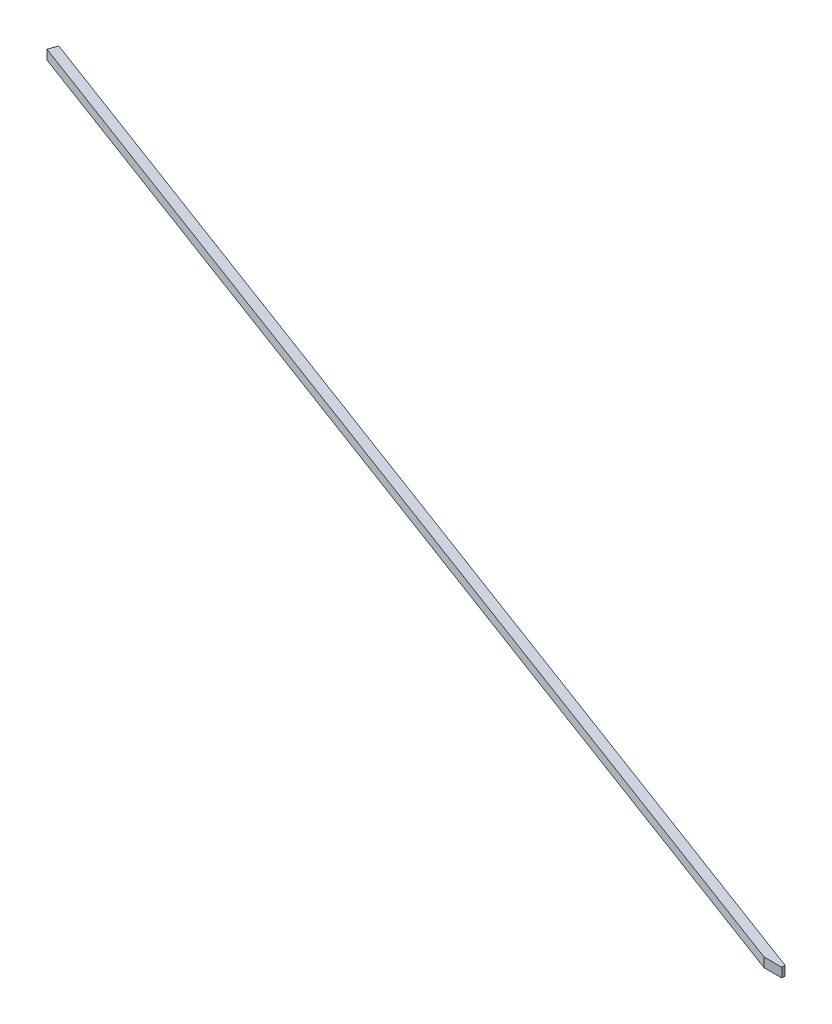
SolidWorks part; units mm, degrees
note: The reader was unsure of these and kept them because the rebuilt part matched: shared geometry of "Sketch5<3>".
material "Balsa"
ref_plane "Front Plane" through (0, 0, 0) normal (0, 0, 1) x (1, 0, 0)
ref_plane "Top Plane" through (0, 0, 0) normal (0, 1, 0) x (1, 0, 0)
ref_plane "Right Plane" through (0, 0, 0) normal (1, 0, 0) x (0, 0, -1)
sketch "Sketch1" plane through (0, 0, 0) normal (0, 0, 1) x (1, 0, 0)
  line L0 (-18.175, 48.175) -> (18.175, 48.175)
  line L4 (405, 11.825) -> (405, 15)
  line L5 (-15, 45) -> (15, 45)
  line L7 (-15, 15) -> (15, 15)
  line L10 (405, 11.825) -> (405, 15)
  line L14 (-18.175, 11.825) -> (18.175, 11.825)
  line L16 (18.175, 48.175) -> (405, 48.175)
  line L17 (18.175, 11.825) -> (405, 11.825)
  line L18 (15, 45) -> (405, 45)
  line L19 (15, 15) -> (405, 15)
  line L20 (-18.175, 48.175) -> (-18.175, 45)
  line L21 (-18.175, 48.175) -> (-18.175, 11.825) construction
  line L22 (-15, 45) -> (-15, 15) construction
  line L23 (15, 45) -> (15, 15) construction
  line L24 (-18.175, 45) -> (-15, 45)
  line L25 (18.175, 48.175) -> (18.175, 11.825) construction
  line L26 (405, 45) -> (405, 48.175)
  line L27 (405, 45) -> (405, 48.175)
  line L28 (-18.175, 11.825) -> (-18.175, 15)
  line L29 (-18.175, 15) -> (-15, 15)
  point P4 (0, 30)
  dimension "D3" = 30
  dimension "D5" = 3.175
extrude "Boss-Extrude1" add sketch "Sketch1" along normal blind 3.175 contours L18 L26 L16 L0 L20 L24 L5 | L29 L28 L14 L17 L4 L19 L7
sketch "Sketch2" plane through (0, 0, 3.175) normal (0, 0, 1) x (1, 0, 0)
  line L0 (-18.175, 48.175) -> (405, 48.175) construction
  line L1 (-18.175, 11.825) -> (-15, 11.825)
  line L2 (-18.175, 11.825) -> (-18.175, 48.175)
  line L3 (-18.175, 48.175) -> (-15, 48.175)
  line L4 (-15, 11.825) -> (-15, 48.175)
  line L5 (-18.175, 11.825) -> (405, 11.825) construction
  line L6 (-15, 48.175) -> (15, 48.175)
  line L7 (-15, 48.175) -> (-15, 11.825)
  line L8 (-15, 11.825) -> (15, 11.825)
  line L9 (15, 48.175) -> (15, 11.825)
  line L10 (18.175, 30) -> (401.825, 30) construction
  line L11 (15, 48.175) -> (18.175, 48.175)
  line L12 (15, 48.175) -> (15, 11.825)
  line L13 (15, 11.825) -> (18.175, 11.825)
  line L14 (18.175, 48.175) -> (18.175, 11.825)
  line L15 (405, 48.175) -> (401.825, 48.175)
  line L16 (405, 48.175) -> (405, 11.825)
  line L17 (405, 11.825) -> (401.825, 11.825)
  line L18 (401.825, 48.175) -> (401.825, 11.825)
  line L19 (210, 30) -> (210, 38.7375) construction
  line L20 (18.175, 38.7375) -> (210, 38.7375) construction
  line L21 (114.0875, 38.7375) -> (114.0875, 45)
  line L22 (-18.175, 45) -> (405, 45) construction
  line L23 (210, 38.7375) -> (401.825, 38.7375) construction
  line L24 (305.9125, 38.7375) -> (305.9125, 45) construction
  line L25 (115.675, 11.825) -> (120.0251, 11.825)
  line L26 (115.675, 11.825) -> (112.5, 11.825)
  line L27 (115.675, 11.825) -> (115.675, 48.175)
  line L28 (114.1836, 48.175) -> (112.5, 48.175)
  line L29 (112.5, 11.825) -> (112.5, 48.175)
  line L30 (114.0875, 30) -> (113.3243, 38.7375) construction
  line L31 (115.675, 48.175) -> (112.5, 11.825) construction
  line L32 (211.5875, 11.825) -> (208.4125, 11.825)
  line L33 (211.5875, 11.825) -> (211.5875, 48.175)
  line L34 (211.5875, 48.175) -> (208.4125, 48.175)
  line L35 (208.4125, 11.825) -> (208.4125, 48.175)
  line L36 (211.5875, 11.825) -> (209.2368, 38.7375) construction
  line L37 (211.5875, 48.175) -> (208.4125, 11.825) construction
  line L38 (304.325, 11.825) -> (307.5, 11.825)
  line L39 (304.325, 11.825) -> (304.325, 48.175)
  line L40 (304.325, 48.175) -> (307.5, 48.175)
  line L41 (307.5, 11.825) -> (307.5, 48.175)
  line L42 (304.325, 11.825) -> (307.5, 48.175) construction
  line L43 (304.325, 48.175) -> (307.5, 11.825) construction
  line L44 (120.0251, 11.825) -> (208.4125, 46.4699)
  line L45 (111.3249, 11.825) -> (112.5417, 12.3019)
  line L46 (208.4125, 48.175) -> (204.0624, 48.175)
  line L47 (115.675, 13.5301) -> (204.0624, 48.175)
  point P36 (114.0875, 30)
  point P45 (305.9125, 30)
  line B0 (22.5897, 11.825) -> (112.5, 46.4737)
  line B1 (18.175, 13.5263) -> (108.0853, 48.175)
  line B2 (108.0853, 48.175) -> (112.5, 48.175)
  line B3 (18.175, 11.825) -> (22.5897, 11.825)
  line B4 (211.5875, 11.825) -> (215.9376, 11.825)
  line B5 (215.9376, 11.825) -> (304.325, 46.4699)
  line B6 (304.325, 48.175) -> (299.9749, 48.175)
  line B7 (211.5875, 13.5301) -> (299.9749, 48.175)
  line B8 (311.9147, 11.825) -> (401.825, 46.4737)
  line B9 (307.5, 13.5263) -> (397.4103, 48.175)
  line B10 (397.4103, 48.175) -> (401.825, 48.175)
  line B11 (307.5, 11.825) -> (311.9147, 11.825)
  dimension "D1" = 3.175
  dimension "D2" = 30
  dimension "D3" = 3.175
  dimension "D4" = 3.175
  dimension "D5" = 3.175
  dimension "D6" = 3.175
  dimension "D7" = 3.175
  dimension "D8" = 0
  dimension "D10" = 0
  dimension "D9" = 0
  dimension "D11" = 0
sketch_block_instance "Block1-1"
sketch_block "Block1"
sketch_block_instance "Block2-1"
sketch_block "Block2"
sketch_block_instance "Block1-3"
extrude "Boss-Extrude2" add sketch "Sketch2" along normal blind 3.175
sketch "Sketch3" plane through (405, 0, 0) normal (1, 0, 0) x (0, 0, -1)
  line L1 (-6.35, 11.825) -> (-3.175, 11.825)
  line L2 (-6.35, 11.825) -> (-6.35, 8.65)
  line L3 (-6.35, 8.65) -> (-3.175, 8.65)
  line L4 (-3.175, 11.825) -> (-3.175, 8.65)
  line L5 (-6.35, 48.175) -> (-3.175, 48.175)
  line L6 (-6.35, 48.175) -> (-6.35, 51.35)
  line L7 (-6.35, 51.35) -> (-3.175, 51.35)
  line L8 (-3.175, 48.175) -> (-3.175, 51.35)
  line M2 (0, 48.175) -> (-6.35, 48.175)
  line M4 (-6.35, 11.825) -> (0, 11.825)
  dimension "D1" = 3.175
  dimension "D2" = 3.175
extrude "Boss-Extrude8" add sketch "Sketch3" against normal up to surface (423.175 mm away) separate body contours L8 L7 L6 M2 | L4 L2 L3 M4 up to face at (-18.175, 30, 2.3812)
sketch "Sketch4" plane through (405, 0, 0) normal (1, 0, 0) x (0, 0, -1)
  line L1 (-3.175, 48.175) -> (0, 48.175)
  line L2 (-3.175, 48.175) -> (-3.175, 11.825)
  line L3 (-3.175, 11.825) -> (0, 11.825)
  line L4 (0, 48.175) -> (0, 11.825)
extrude "Cut-Extrude1" cut sketch "Sketch4" against normal through all
sketch "Sketch5" plane through (0, 8.65, 0) normal (0, -1, 0) x (1, 0, 0)
  line L0 (-18.175, 6.35) -> (-18.175, -138.65)
  line L1 (391.037, 3.175) -> (399.5367, 6.35)
  line L2 (381.9636, 3.175) -> (390.4633, 6.35)
  line L3 (-18.175, 6.35) -> (405, 6.35) construction
  line L4 (-19.7625, 6.35) -> (-19.7625, -140.2375)
  line L5 (399.5367, 6.35) -> (390.4633, 6.35)
  line L6 (10.3548, -139.0261) -> (391.037, 3.175)
  line L7 (-16.5875, 6.35) -> (-16.5875, -137.0625)
  line L8 (399.5367, 6.35) -> (413.6665, 33.7017)
  line L9 (9.2438, -136.0518) -> (381.9636, 3.175)
  line L10 (-18.175, 3.175) -> (405, 3.175) construction
  line L11 (-18.175, 6.35) -> (405, 6.35)
  line L12 (-18.175, 3.175) -> (405, 3.175)
  line L13 (7.1118, -140.2375) -> (395.5555, 4.8629) construction
  line L14 (6.825, -138.65) -> (395, 6.35) construction
  line L15 (10.3548, -139.0261) -> (-37.9264, -157.0612)
  line L16 (6.5382, -137.0625) -> (394.4445, 7.8371) construction
  line L17 (-85.8493, 33.7017) -> (390.4633, 6.35)
  line L18 (9.2438, -136.0518) -> (10.3548, -139.0261)
  line L19 (-16.5875, -137.0625) -> (6.5382, -137.0625) construction
  line L20 (-18.175, -138.65) -> (6.825, -138.65) construction
  line L21 (-19.7625, -140.2375) -> (7.1118, -140.2375) construction
  line L23 (413.6665, 33.7017) -> (490.5667, -72.6912)
  line L24 (490.5667, -72.6912) -> (326.282, -178.1783)
  line L25 (326.282, -178.1783) -> (36.2264, -208.2863)
  line L26 (36.2264, -208.2863) -> (10.3548, -139.0261)
  line L28 (-37.9264, -157.0612) -> (-85.8493, 33.7017)
  arc A0 (14.6659, -137.4157) -> (13.5549, -134.4414) centre (6.825, -138.65) ccw
  line M4 (-18.175, 3.175) -> (405, 3.175)
  dimension "D3" = 15.875
  dimension "D1" = 145
  dimension "D2" = 25
  dimension "D5" = 1.5875
  dimension "D6" = 1.5875
extrude "Cut-Extrude5" cut sketch "Sketch5" against normal through all
extrude "Boss-Extrude9" add sketch "Sketch5<3>" against normal blind 3.175 contours A0 L6 L9 M4 | L6 A0 L9 L18
sketch "Sketch5<3>" plane through (0, 8.65, 0) normal (0, -1, 0) x (1, 0, 0) same geometry as "Sketch5"
sketch "Sketch8" plane through (0, 51.35, 0) normal (0, 1, 0) x (1, 0, 0)
  circle A0 centre (390.0312, -4.9575) radius 22.2466
extrude "Cut-Extrude6" cut sketch "Sketch8" against normal blind 30
sketch "Sketch9" plane through (-36.4863, 0, -13.6292) normal (-0.9368, 0, -0.3499) x (-0.3499, 0, 0.9368)
  line L4 (-133.8599, 8.65) -> (-130.6849, 8.65)
  line L5 (-130.6849, 8.65) -> (-130.6849, 11.825)
  line L6 (-130.6849, 11.825) -> (-133.8599, 11.825)
  line L7 (-133.8599, 11.825) -> (-133.8599, 8.65)
  line L8 (-133.8599, 8.65) -> (-130.6849, 8.65)
  line L9 (-130.6849, 8.65) -> (-130.6849, 11.825)
  line L10 (-130.6849, 11.825) -> (-133.8599, 11.825)
  line L11 (-133.8599, 11.825) -> (-133.8599, 8.65)
  dimension "D1" = 0
extrude "Boss-Extrude10" add sketch "Sketch9" along normal blind 9.525
sketch "Sketch10" plane through (0, 8.65, 0) normal (0, -1, 0) x (1, 0, 0)
  line L1 (396.5003, 5.2158) -> (399.5367, 5.2158)
  line L2 (396.5003, 5.2158) -> (396.5003, 6.35)
  line L3 (396.5003, 6.35) -> (399.5367, 6.35)
  line L4 (399.5367, 5.2158) -> (399.5367, 6.35)
extrude "Cut-Extrude7" cut sketch "Sketch10" against normal blind 10 contours L2 L3 L4 L1
